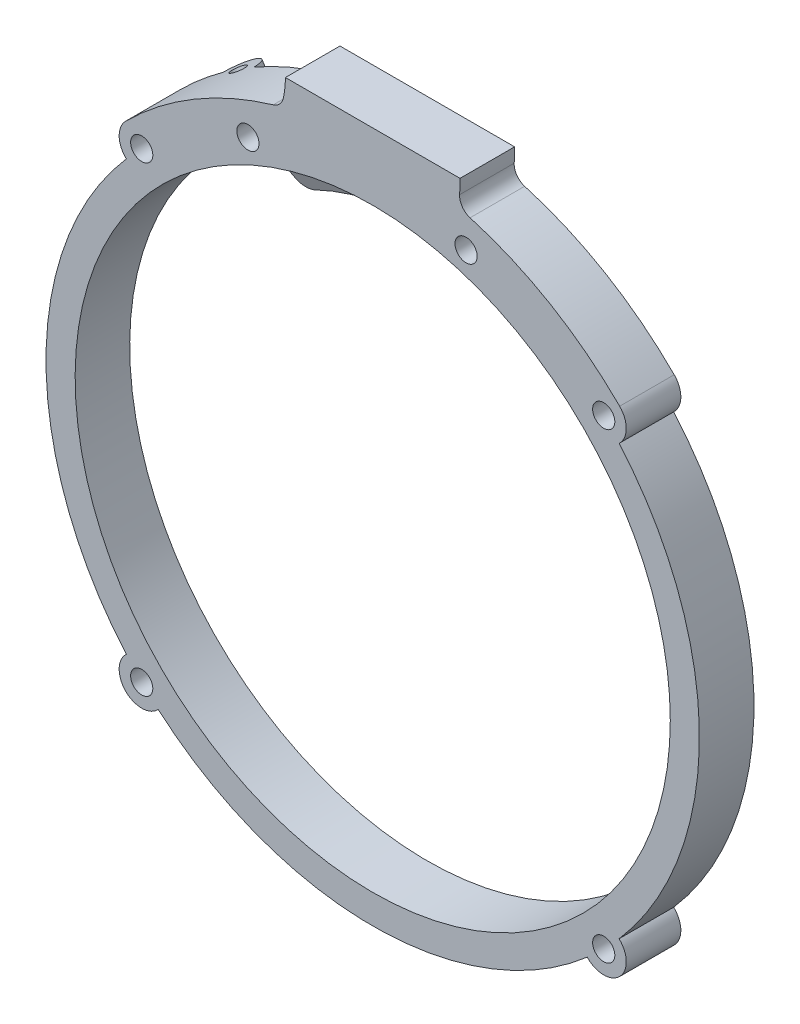
SolidWorks part; units mm, degrees
material "ABS"
ref_plane "前视基准面" through (0, 0, 0) normal (0, 0, 1) x (1, 0, 0)
ref_plane "上视基准面" through (0, 0, 0) normal (0, 1, 0) x (1, 0, 0)
ref_plane "右视基准面" through (0, 0, 0) normal (1, 0, 0) x (0, 0, -1)
sketch "草图1" plane through (0, 0, 0) normal (0, 0, 1) x (1, 0, 0)
  line L0 (0, 0) -> (0, 50.1) construction
  line L1 (0, 50.1) -> (0, 73.1) construction
  line L2 (-35.5, 73.1) -> (35.5, 73.1) construction
  line L3 (-12, 50.1) -> (12, 50.1)
  line L4 (0, 0) -> (12.8351, 41.9818) construction
  line L5 (0, 0) -> (-17.1531, 40.4102) construction
  circle A0 centre (0, 0) radius 19.04 construction
  circle A1 centre (0, 0) radius 40.9
  circle A2 centre (0, 0) radius 21 construction
  circle A3 centre (-14.8492, 14.8492) radius 1.525 construction
  circle A4 centre (14.8492, 14.8492) radius 1.525 construction
  circle A5 centre (14.8492, -14.8492) radius 1.525 construction
  circle A6 centre (-14.8492, -14.8492) radius 1.525 construction
  circle A7 centre (0, 0) radius 46.4 construction
  circle A8 centre (-35.5, 73.1) radius 30 construction
  circle A9 centre (35.5, 73.1) radius 30 construction
  arc A10 (0, 50.1) -> (-6.8598, 33.3008) centre (-24, 50.1) cw construction
  circle A11 centre (0, 0) radius 34 construction
  circle A12 centre (-1.2412, 42.4819) radius 8.5 construction
  circle A13 centre (0, 59.4365) radius 8.5 construction
  arc A15 (-13.6688, 46.0127) -> (13.3851, 46.096) centre (0, 0) ccw
  arc A18 (-12, 50.1) -> (-12.286, 47.4958) centre (-24, 50.1) cw
  arc A19 (12, 50.1) -> (11.9459, 48.1263) centre (-24, 50.1) cw
  arc A20 (-12.286, 47.4958) -> (-13.6688, 46.0127) centre (-14.2383, 47.9298) cw
  arc A21 (11.9459, 48.1263) -> (13.3851, 46.096) centre (13.9428, 48.0166) ccw
  circle A22 centre (-17.1531, 40.4102) radius 1.525
  circle A23 centre (12.8351, 41.9818) radius 1.525
  point P17 (0, 0)
  dimension "D2" = 38.08
  dimension "D3" = 81.8
  dimension "D4" = 42
  dimension "D6" = 3.05
  dimension "D8" = 60
  dimension "D10" = 24
  dimension "D11" = 68
  dimension "D12" = 17
  dimension "D13" = 92.8
  dimension "D14" = 96
  dimension "D16" = 2
  dimension "D17" = 3.05
  dimension "D1" = 50.1
  dimension "D7" = 71
  dimension "D9" = 23
  dimension "D15" = 24
  dimension "D18" = 43.9
  dimension "D19" = 17
  dimension "D20" = 40
  dimension "D5" = 4
extrude "凸台-拉伸1" add sketch "草图1" along normal blind 1.5
sketch "草图2" plane through (0, 0, 1.5) normal (0, 0, 1) x (1, 0, 0)
  line L0 (-19.2014, 36.1126) -> (-17.1212, 32.2004)
  line L1 (-16.4315, 30.9032) -> (0, 0) construction
  line L5 (0, 0) -> (0, 40.9) construction
  line L6 (25.1806, 32.2296) -> (19.2364, 29.9464)
  line L7 (18.5472, 29.6817) -> (0, 0) construction
  line L8 (25.1806, 32.2296) -> (0, 0) construction
  circle A0 centre (0, 0) radius 40.9 construction
  circle A1 centre (0, 0) radius 35 construction
  arc A2 (-17.1212, 32.2004) -> (-15.1476, 31.5523) centre (-15.7968, 32.9046) ccw
  arc A3 (-15.1476, 31.5523) -> (17.9301, 30.0585) centre (0, 0) cw
  arc A4 (17.9301, 30.0585) -> (19.2364, 29.9464) centre (18.6985, 31.3467) ccw
  arc A6 (25.1806, 32.2296) -> (-19.2014, 36.1126) centre (0, 0) ccw
  dimension "D1" = 70
  dimension "D3" = 1.5
  dimension "D6" = 1.5
  dimension "D2" = 28
  dimension "D4" = 6
  dimension "D5" = 60
extrude "凸台-拉伸2" add sketch "草图2" against normal up to surface (1.5 mm away) up to face at (-15.6281, 40.4102, 0)
sketch "草图3" plane through (0, 0, 1.5) normal (0, 0, 1) x (1, 0, 0)
  circle A0 centre (0, 0) radius 44.9 construction
  circle A1 centre (-31.7491, 31.7491) radius 1.525
  circle A2 centre (31.7491, 31.7491) radius 1.525
  circle A3 centre (31.7491, -31.7491) radius 1.525
  circle A4 centre (-31.7491, -31.7491) radius 1.525
  point P15 (0, 0)
  dimension "D2" = 3.05
  dimension "D3" = 89.8
  dimension "D1" = 4
extrude "切除-拉伸1" cut sketch "草图3" against normal blind 10
sketch "草图4" plane through (0, 0, 1.5) normal (0, 0, 1) x (1, 0, 0)
  line L1 (12, 50.1) -> (-12, 50.1)
  line L2 (12, 50.1) -> (-12, 50.1)
  circle A0 centre (-31.7491, -31.7491) radius 1.525 construction
  circle A1 centre (31.7491, -31.7491) radius 1.525 construction
  circle A2 centre (31.7491, 31.7491) radius 1.525 construction
  circle A3 centre (12.8351, 41.9818) radius 1.525 construction
  circle A4 centre (-31.7491, 31.7491) radius 1.525 construction
  arc A5 (-13.6688, 46.0127) -> (-12.286, 47.4958) centre (-14.2383, 47.9298) ccw
  arc A6 (-13.6688, 46.0127) -> (13.3851, 46.096) centre (0, 0) ccw
  arc A7 (11.9459, 48.1263) -> (13.3851, 46.096) centre (13.9428, 48.0166) ccw
  arc A8 (11.9459, 48.1263) -> (12, 50.1) centre (-24, 50.1) ccw
  arc A9 (-12.286, 47.4958) -> (-12, 50.1) centre (-24, 50.1) ccw
  arc A10 (-13.6688, 46.0127) -> (-12.286, 47.4958) centre (-14.2383, 47.9298) ccw
  arc A11 (-13.6688, 46.0127) -> (13.3851, 46.096) centre (0, 0) ccw
  arc A12 (11.9459, 48.1263) -> (13.3851, 46.096) centre (13.9428, 48.0166) ccw
  arc A13 (11.9459, 48.1263) -> (12, 50.1) centre (-24, 50.1) ccw
  arc A14 (-12.286, 47.4958) -> (-12, 50.1) centre (-24, 50.1) ccw
  circle A15 centre (-17.1531, 40.4102) radius 1.525 construction
  circle A16 centre (-31.7491, -31.7491) radius 1.525
  circle A17 centre (31.7491, -31.7491) radius 1.525
  circle A18 centre (31.7491, 31.7491) radius 1.525
  circle A19 centre (12.8351, 41.9818) radius 1.525
  circle A20 centre (-31.7491, 31.7491) radius 1.525
  circle A21 centre (-17.1531, 40.4102) radius 1.525
  circle A22 centre (0, 0) radius 40.9
  arc A23 (-19.2014, 36.1126) -> (25.1806, 32.2296) centre (0, 0) ccw construction
  dimension "D1" = 0
extrude "凸台-拉伸3" add sketch "草图4" along normal blind 6
sketch "草图5" plane through (0, 0, 7.5) normal (0, 0, 1) x (1, 0, 0)
  line L0 (0, 0) -> (0, -40.9)
  arc A0 (-33.9411, 33.9411) -> (-33.8641, 29.4827) centre (-31.7491, 31.7491) ccw
  arc A1 (-13.6688, 46.0127) -> (13.3851, 46.096) centre (0, 0) ccw construction
  arc A2 (-33.8641, -29.4827) -> (-29.4827, -33.8641) centre (-31.7491, -31.7491) ccw
  arc A3 (-33.8641, 29.4827) -> (-33.8641, -29.4827) centre (0, 0) ccw
  circle A4 centre (0, 0) radius 40.9 construction
  arc A5 (-29.4827, -33.8641) -> (29.4827, -33.8641) centre (0, 0) ccw
  arc A6 (33.8641, 29.4827) -> (33.8641, -29.4827) centre (0, 0) cw
  arc A7 (33.8641, -29.4827) -> (29.4827, -33.8641) centre (31.7491, -31.7491) cw
  arc A8 (33.9411, 33.9411) -> (33.8641, 29.4827) centre (31.7491, 31.7491) cw
  arc A9 (-33.9411, 33.9411) -> (33.9411, 33.9411) centre (0, 0) ccw
  arc M5 (-13.6688, 46.0127) -> (13.3851, 46.096) centre (0, 0) ccw
extrude "切除-拉伸2" cut sketch "草图5" against normal through all and the other way through all contours A3 A0 A2 M5 | A7 A5 A2 M5 | A8 A6 A7 M5 region at (35.5419, -31.6836, 7.5) region at (-31.6836, -35.5419, 7.5) region at (-35.5419, 31.6836, 7.5)
sketch "草图6" plane through (0, 0, 0) normal (0, 0, -1) x (-1, 0, 0)
  line L0 (20, 35.6765) -> (24.2038, 32.9695)
  arc A0 (-25.1806, 32.2296) -> (19.2014, 36.1126) centre (0, 0) ccw construction
  arc A1 (24.2038, 32.9695) -> (20, 35.6765) centre (0, 0) ccw
  dimension "D1" = 5
  dimension "D2" = 20
extrude "凸台-拉伸4" add sketch "草图6" against normal blind 2.5
sketch "草图8" plane through (-22.1019, 34.323, 0) normal (0.5414, -0.8408, 0) x (0.8408, 0.5414, 0)
  line L0 (2.5, 0) -> (-2.5, 0) construction
  line L1 (-2.5, 0) -> (2.5, 0)
  line L4 (-2.5, 2.5) -> (2.5, 2.5) construction
  line L5 (2.5, 0) -> (-2.5, 0) construction
  arc A1 (-2.5, 0) -> (2.5, 0) centre (0, 0) ccw
extrude "凸台-拉伸5" add sketch "草图8" against normal up to surface (7.1113 mm away) up to face at (-24.1816, 40.6094, 3.75)
sketch "草图9" plane through (-22.1019, 34.323, 0) normal (0.5414, -0.8408, 0) x (0.8408, 0.5414, 0)
  circle A0 centre (0, 0) radius 1
  arc A1 (-2.5, 0) -> (2.5, 0) centre (0, 0) ccw construction
  dimension "D1" = 2
extrude "切除-拉伸3" cut sketch "草图9" against normal through all
chamfer "倒角1" distance 1.2 angle 67 1 edges at (1.5791, 34.9644, 1.5) tangent propagation no first distance on face at (1.4852, 32.8849, 0.75)
chamfer "倒角2" distance 3 angle 20 1 edges at (3.5647, 40.7444, 1.5) first distance on face at (2.7323, 36.2077, 1.5)
